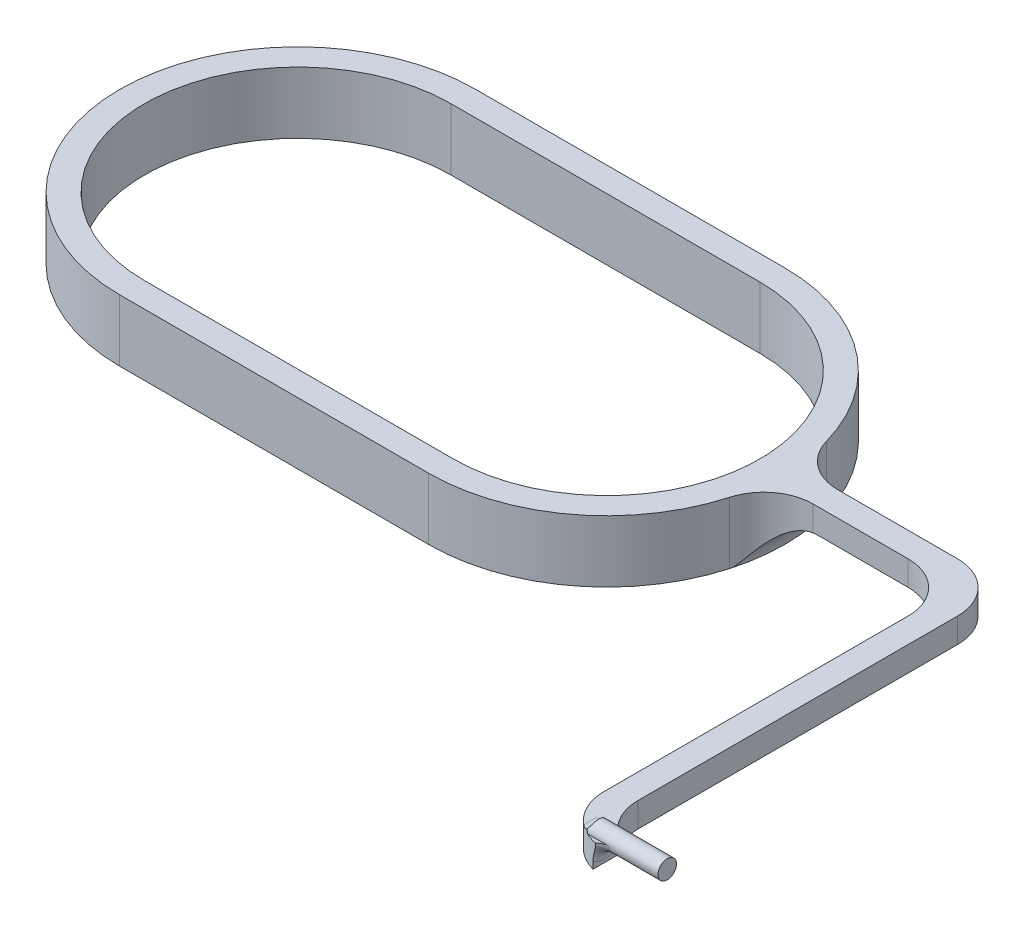
SolidWorks part; units mm, degrees
ref_plane "Front Plane" through (0, 0, 0) normal (0, 0, 1) x (1, 0, 0)
ref_plane "Top Plane" through (0, 0, 0) normal (0, 1, 0) x (1, 0, 0)
ref_plane "Right Plane" through (0, 0, 0) normal (1, 0, 0) x (0, 0, -1)
sketch "Sketch1" plane through (0, 0, 0) normal (0, 1, 0) x (1, 0, 0)
  line L0 (0, 0) -> (25, 0) construction
  line L1 (0, 12.4) -> (25, 12.4)
  line L2 (0, -12.4) -> (25, -12.4)
  line L3 (0, 0) -> (25, 0) construction
  line L4 (0, 14.4) -> (25, 14.4)
  line L5 (0, -14.4) -> (25, -14.4)
  arc A0 (0, 12.4) -> (0, -12.4) centre (0, 0) ccw
  arc A1 (25, -12.4) -> (25, 12.4) centre (25, 0) ccw
  arc A2 (0, 14.4) -> (0, -14.4) centre (0, 0) ccw
  arc A3 (25, -14.4) -> (25, 14.4) centre (25, 0) ccw
  point P3 (12.5, 0)
  point P10 (12.5, 0)
  dimension "D1" = 24.8
  dimension "D2" = 25
  dimension "D3" = 2
extrude "Boss-Extrude1" add sketch "Sketch1" along normal blind 5
sketch "Sketch2" plane through (0, 5, 0) normal (0, -1, 0) x (1, 0, 0)
  line L1 (37.4, -1) -> (56.4, -1)
  line L2 (37.4, -1) -> (37.4, 1)
  line L3 (37.4, 1) -> (56.4, 1)
  line L4 (56.4, -1) -> (56.4, 1)
  line L5 (56.4, -1) -> (54.4, -1)
  line L6 (56.4, -1) -> (56.4, 33.5)
  line L7 (56.4, 33.5) -> (54.4, 33.5)
  line L8 (54.4, -1) -> (54.4, 33.5)
  line L9 (54.4, 33.5) -> (57.4, 33.5)
  line L10 (54.4, 33.5) -> (54.4, 31.5)
  line L11 (54.4, 31.5) -> (57.4, 31.5)
  line L12 (57.4, 33.5) -> (57.4, 31.5)
  arc A0 (25, -12.4) -> (25, 12.4) centre (25, 0) ccw construction
  arc A1 (25, -14.4) -> (25, 14.4) centre (25, 0) ccw construction
  point P10 (37.4, 0)
  point P18 (39.4, 0)
  point P19 (57.4, 32.5)
  arc M29 (25, 14.4) -> (25, -14.4) centre (25, 0) cw
  dimension "D1" = 15
  dimension "D2" = 2
  dimension "D3" = 2
  dimension "D4" = 2
  dimension "D5" = 32.5
  dimension "D6" = 1
extrude "Boss-Extrude2" add sketch "Sketch2" along normal blind 2 contours L8 L1 L3 M29 | L2 L3 L1 M29 | L1 L8 L3 L4 | L8 L11 L6 L3 | L11 L8 L7 L6 | L9 L12 L11 L6 region at (55.4, 5, 0) region at (46.8942, 5, 0) region at (38.3942, 5, 0) region at (55.4, 5, 16.25) region at (55.4, 5, 32.5) region at (56.9, 5, 32.5)
fillet "Fillet1" radius 4 7 edges at (39.4, 3, 0) (39.3652, 4, 1) (39.3652, 4, -1) (56.4, 4, -1) (54.4, 4, 1) (54.4, 4, 33.5) (56.4, 4, 31.5)
sketch "Sketch3" plane through (57.4, 0, 0) normal (1, 0, 0) x (0, 0, -1)
  line L1 (-33.5, 5) -> (-31.5, 5) construction
  line L3 (-33.5, 5) -> (-31.5, 5) construction
  circle A0 centre (-32.5, 5) radius 0.75
  point P8 (-32.5, 5)
  dimension "D1" = 1.5
extrude "Boss-Extrude3" add sketch "Sketch3" along normal blind 5 and the other way blind 0.5 contours A0
fillet "Fillet2" radius 1 2 edges at (56.9, 5, 32.5) (57.4, 4.25, 32.5)
